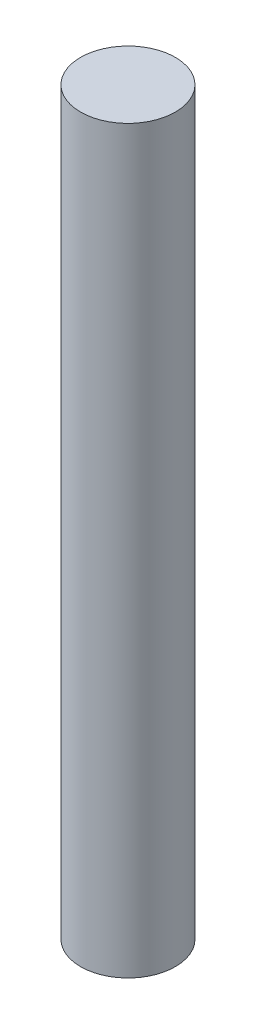
SolidWorks part; units mm, degrees
ref_plane "Front Plane" through (0, 0, 0) normal (0, 0, 1) x (1, 0, 0)
ref_plane "Top Plane" through (0, 0, 0) normal (0, 1, 0) x (1, 0, 0)
ref_plane "Right Plane" through (0, 0, 0) normal (1, 0, 0) x (0, 0, -1)
sketch "Sketch1" plane through (0, 0, 0) normal (0, 1, 0) x (1, 0, 0)
  circle A0 centre (0, 0) radius 3.9688
  dimension "D1" = 7.9375
extrude "Boss-Extrude1" add sketch "Sketch1" along normal blind 61.976
scale "Scale1" scale about centroid uniform scaling yes scale factor 0.75
